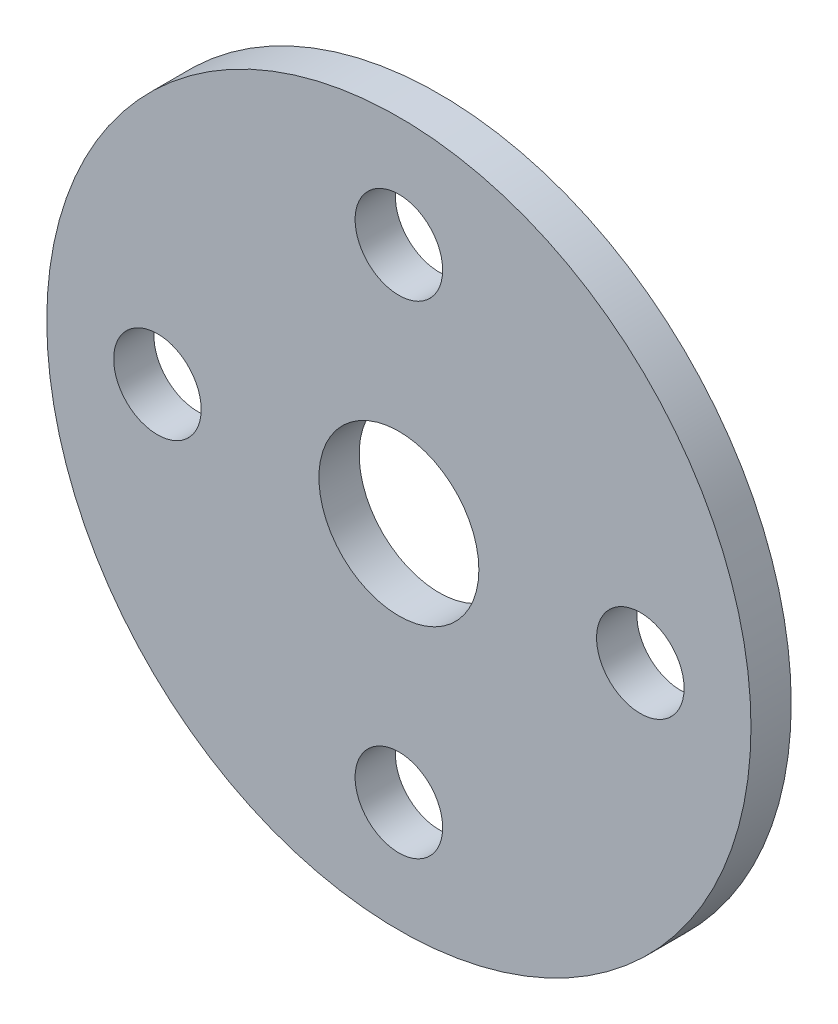
SolidWorks part; units mm, degrees
ref_plane "Front Plane" through (0, 0, 0) normal (0, 0, 1) x (1, 0, 0)
ref_plane "Top Plane" through (0, 0, 0) normal (0, 1, 0) x (1, 0, 0)
ref_plane "Right Plane" through (0, 0, 0) normal (1, 0, 0) x (0, 0, -1)
sketch "Sketch1" plane through (0, 0, 0) normal (0, 0, 1) x (1, 0, 0)
  circle A0 centre (0, 0) radius 17.5
  circle A2 centre (12, 0) radius 2.175
  circle A3 centre (0, 12) radius 2.175
  circle A4 centre (-12, 0) radius 2.175
  circle A5 centre (0, -12) radius 2.175
  circle A6 centre (0, 0) radius 3.975
  dimension "D1" = 4.35
  dimension "D2" = 4.35
  dimension "D3" = 4.35
  dimension "D4" = 4.35
  dimension "D5" = 7.95
  dimension "D6" = 12
extrude "Boss-Extrude1" add sketch "Sketch1" along normal blind 2
